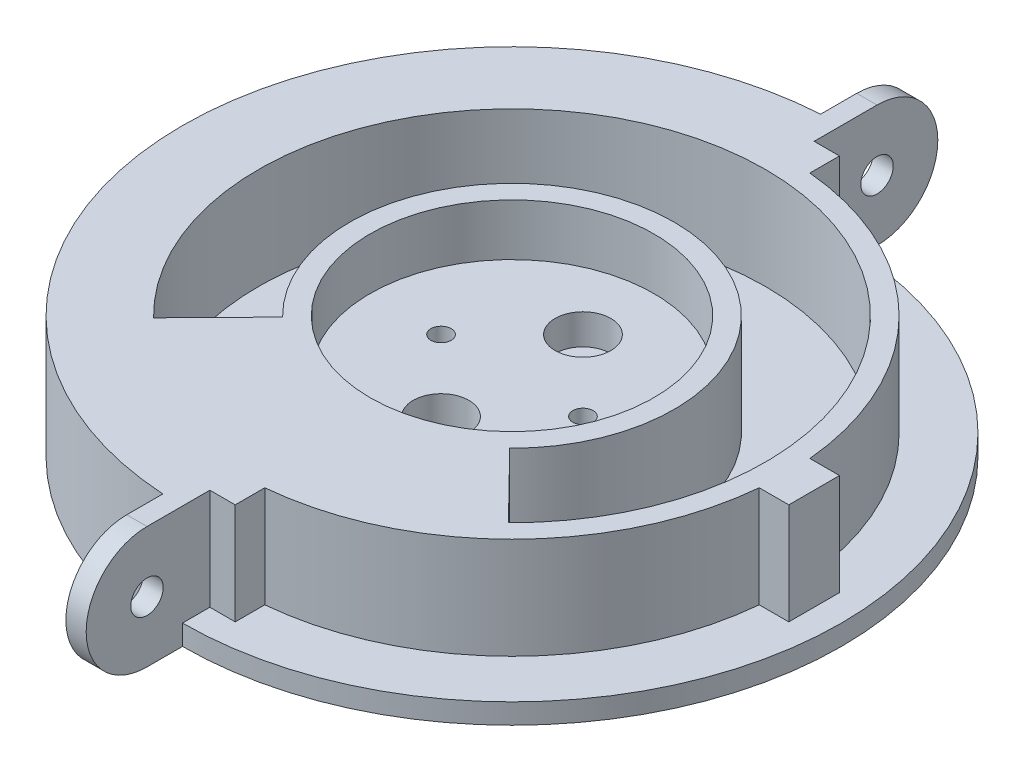
SolidWorks part; units mm, degrees
ref_plane "Front Plane" through (0, 0, 0) normal (0, 0, 1) x (1, 0, 0)
ref_plane "Top Plane" through (0, 0, 0) normal (0, 1, 0) x (1, 0, 0)
ref_plane "Right Plane" through (0, 0, 0) normal (1, 0, 0) x (0, 0, -1)
sketch "Sketch1" plane through (0, 0, 0) normal (0, 1, 0) x (1, 0, 0)
  line L0 (-17.5, -17.8536) -> (-11.2, -11.4263)
  line L1 (0, -55) -> (0, 55) construction
  line L2 (17.5, -17.8536) -> (11.2, -11.4263)
  line L4 (-17.5, -17.8536) -> (3.8221, -38.7535) construction
  circle A0 centre (0, 0) radius 27
  arc A1 (11.2, -11.4263) -> (-11.2, -11.4263) centre (0, 0) ccw
  arc A2 (17.5, -17.8536) -> (-17.5, -17.8536) centre (0, 0) ccw
  circle A3 centre (0, 0) radius 14
  arc A4 (16.5039, 11.7639) -> (14.35, -14.6399) centre (0.1913, -0.1952) cw construction
  circle A5 centre (0, 0) radius 19.9533 construction
  dimension "D1" = 54
  dimension "D2" = 2
  dimension "D3" = 9
  dimension "D4" = 2
  dimension "D5" = 35
extrude "Boss-Extrude1" add sketch "Sketch1" along normal blind 10
sketch "Sketch2" plane through (0, 0, 0) normal (0, -1, 0) x (1, 0, 0)
  circle A0 centre (0, 0) radius 32.5
  circle A1 centre (0, 0) radius 14 construction
  circle A2 centre (0, 0) radius 14 construction
  dimension "D1" = 65
extrude "Boss-Extrude2" add sketch "Sketch2" along normal blind 2
sketch "Sketch3" plane through (0, 0, 0) normal (0, 1, 0) x (1, 0, 0)
  line L0 (0, -5.5) -> (0, 5.5) construction
  line L1 (-2.5, 29.8) -> (2.5, 29.8)
  line L2 (-2.5, 29.8) -> (-2.5, 25.4032)
  line L3 (-2.5, 25.4032) -> (2.5, 25.4032)
  line L4 (2.5, 29.8) -> (2.5, 25.4032)
  line L5 (-2.5, 29.8) -> (2.5, 25.4032) construction
  line L6 (-2.5, 25.4032) -> (2.5, 29.8) construction
  line L7 (29.8, 2.5) -> (25.4032, 2.5)
  line L8 (29.8, 2.5) -> (29.8, -2.5)
  line L9 (29.8, -2.5) -> (25.4032, -2.5)
  line L10 (25.4032, 2.5) -> (25.4032, -2.5)
  line L11 (2.5, -29.8) -> (2.5, -25.4032)
  line L12 (2.5, -29.8) -> (-2.5, -29.8)
  line L13 (-2.5, -29.8) -> (-2.5, -25.4032)
  line L14 (2.5, -25.4032) -> (-2.5, -25.4032)
  line L15 (-29.8, -2.5) -> (-25.4032, -2.5)
  line L16 (-29.8, -2.5) -> (-29.8, 2.5)
  line L17 (-29.8, 2.5) -> (-25.4032, 2.5)
  line L18 (-25.4032, -2.5) -> (-25.4032, 2.5)
  circle A1 centre (0, 0) radius 27 construction
  point P0 (0, 27.6016)
  dimension "D2" = 29.8
  dimension "D1" = 5
  dimension "D3" = 4
extrude "Boss-Extrude3" add sketch "Sketch3" along normal blind 10
sketch "Sketch5" plane through (0, 0, 0) normal (0, 1, 0) x (1, 0, 0)
  line L0 (0, 29.8) -> (0, 32.5)
  line L1 (2.5, 29.8) -> (-2.5, 29.8) construction
  line L2 (0, -6.6) -> (0, 6.6) construction
  line L3 (0, -29.8) -> (0, -32.5)
  line L4 (0, 29.8) -> (-2.5, 29.8)
  line L5 (-2.5, 29.8) -> (-2.5, 26.884)
  line L6 (-26.884, 2.5) -> (-29.8, 2.5)
  line L7 (-29.8, 2.5) -> (-29.8, -2.5)
  line L8 (-29.8, -2.5) -> (-26.884, -2.5)
  line L9 (-2.5, -26.884) -> (-2.5, -29.8)
  line L10 (-2.5, -29.8) -> (0, -29.8)
  line L11 (-2.5, -29.8) -> (2.5, -29.8) construction
  circle A0 centre (0, 0) radius 32.5 construction
  arc A1 (0, 32.5) -> (0, -32.5) centre (0, 0) ccw
  arc A2 (-26.884, 2.5) -> (-2.5, 26.884) centre (0, 0) cw
  arc A3 (-26.884, -2.5) -> (-2.5, -26.884) centre (0, 0) ccw
extrude "Boss-Extrude4" add sketch "Sketch5" along normal up to surface (10 mm away) up to face at (0, 10, 0)
ref_plane "Plane1" through (0, 4.9, 0) normal (0, 1, 0) x (1, 0, 0)
sketch "Sketch6" plane through (0, 4.9, 0) normal (0, 1, 0) x (1, 0, 0)
  circle A0 centre (0, 0) radius 14
extrude "Boss-Extrude5" add sketch "Sketch6" against normal up to surface (4.9 mm away) up to face at (0, 0, 14)
sketch "Sketch4" plane through (0, -2, 0) normal (0, -1, 0) x (1, 0, 0)
  circle A0 centre (0, 0) radius 7 construction
  circle A1 centre (0, -7) radius 1
  circle A2 centre (-7, 0) radius 1
  circle A3 centre (0, 7) radius 1
  circle A4 centre (7, 0) radius 1
  point P14 (0, 0)
  dimension "D1" = 14
  dimension "D2" = 2
  dimension "D3" = 4
extrude "Cut-Extrude1" cut sketch "Sketch4" against normal through all both and the other way through all
sketch "Sketch7" plane through (0, 10, 0) normal (0, 1, 0) x (1, 0, 0)
  line L0 (11.2, -11.4263) -> (17.5, -17.8536) construction
  circle A0 centre (0, 0) radius 20.5 construction
  circle A1 centre (0, -20.5) radius 1.6
  point P5 (14.35, -14.6399)
  dimension "D1" = 3.2
extrude "Cut-Extrude2" [suppressed] cut sketch "Sketch7" against normal through all both and the other way through all
sketch "Sketch8" [suppressed] plane through (0, -2, 0) normal (0, -1, 0) x (1, 0, 0)
  line L0 (6.6, 0) -> (-6.6, 0) construction
  line L1 (-3.1177, 20.5) -> (-1.5588, 17.8)
  line L2 (-1.5588, 17.8) -> (1.5588, 17.8)
  line L3 (1.5588, 17.8) -> (3.1177, 20.5)
  line L4 (3.1177, 20.5) -> (1.5588, 23.2)
  line L5 (1.5588, 23.2) -> (-1.5588, 23.2)
  line L6 (-1.5588, 23.2) -> (-3.1177, 20.5)
  circle A0 centre (0, 20.5) radius 2.7 construction
  dimension "D1" = 5.4
extrude "Cut-Extrude3" [suppressed] cut sketch "Sketch8" against normal blind 4
sketch "Sketch9" plane through (0, 0, 0) normal (1, 0, 0) x (0, 0, -1)
  line L0 (32.5, 10) -> (-32.5, 10) construction
  line L1 (36, -2) -> (30.5, -2)
  line L3 (36, 10) -> (30.5, 10)
  line L4 (30.5, -2) -> (30.5, 10)
  line L5 (32.5, 10) -> (32.5, 0) construction
  arc A0 (36, -2) -> (36, 10) centre (36, 4) ccw
  circle A1 centre (36, 4) radius 1.6
  circle A2 centre (36, 4) radius 3 construction
  dimension "D4" = 3.2
  dimension "D5" = 6
  dimension "D1" = 3.5
  dimension "D2" = 2
  dimension "D3" = 12
extrude "Boss-Extrude6" add sketch "Sketch9" against normal blind 2
mirror "Mirror1" about plane through (0, 0, 0) normal (0, 0, 1) of "Boss-Extrude6"
sketch "Sketch10" plane through (0, 4.9, 0) normal (0, 1, 0) x (1, 0, 0)
  circle A0 centre (0, 7) radius 2.75
  circle A1 centre (0, -7) radius 2.75
  dimension "D1" = 5.5
  dimension "D2" = 5.5
extrude "Cut-Extrude4" cut sketch "Sketch10" against normal blind 3
